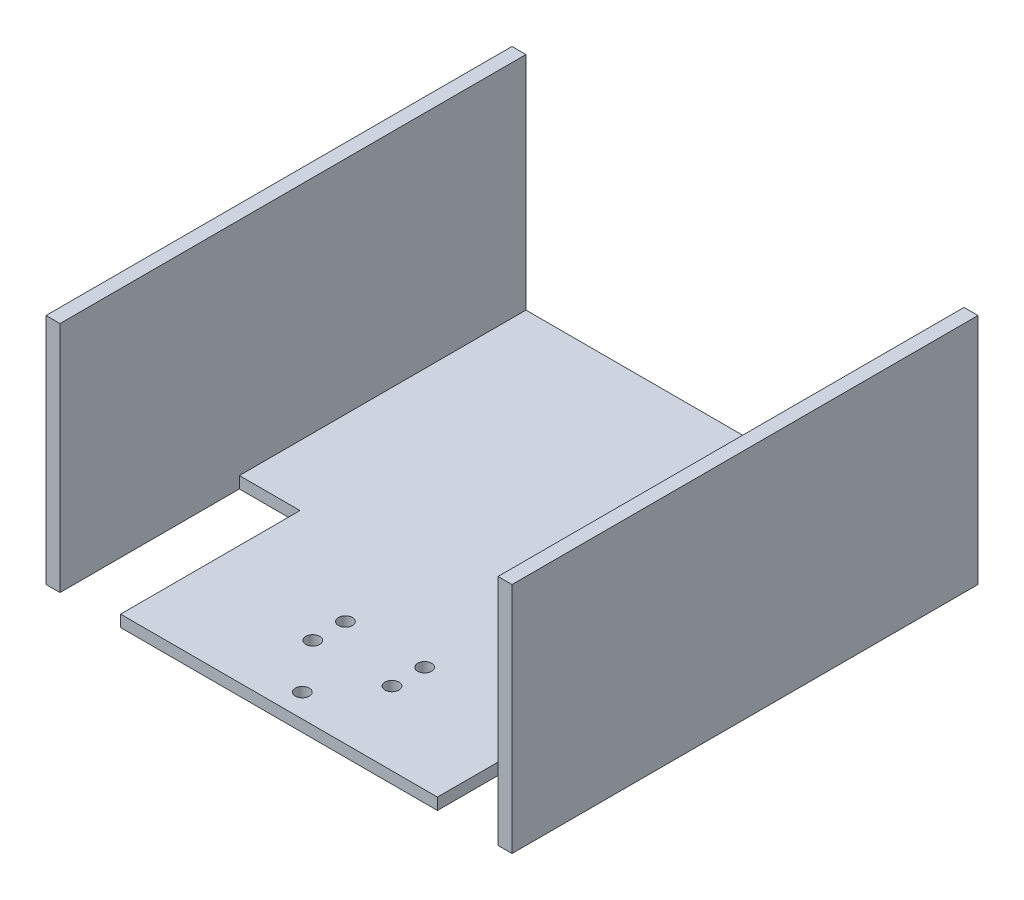
SolidWorks part; units mm, degrees
ref_plane "Alzado" through (0, 0, 0) normal (0, 0, 1) x (1, 0, 0)
ref_plane "Planta" through (0, 0, 0) normal (0, 1, 0) x (1, 0, 0)
ref_plane "Vista lateral" through (0, 0, 0) normal (1, 0, 0) x (0, 0, -1)
sketch "Croquis1" plane through (0, 0, 0) normal (0, 0, 1) x (1, 0, 0)
  line L0 (50, 0) -> (-50, 0)
  line L1 (-50, 0) -> (-50, 50)
  line L2 (-50, 50) -> (-47, 50)
  line L3 (-47, 50) -> (-47, 2.5)
  line L4 (-47, 2.5) -> (47, 2.5)
  line L5 (0, 2.5) -> (0, 0)
  line L6 (0, 0) -> (0, 13.9963) construction
  line L7 (47, 50) -> (47, 2.5)
  line L8 (50, 50) -> (47, 50)
  line L9 (50, 0) -> (50, 50)
  dimension "D1" = 50
  dimension "D2" = 50
  dimension "D3" = 3
  dimension "D4" = 2.5
extrude "Saliente-Extruir1" add sketch "Croquis1" against normal blind 100 contours L4 L7 L8 L9 L0 L1 L2 L3
sketch "Croquis2" plane through (0, 2.5, 0) normal (0, 1, 0) x (1, 0, 0)
  line L0 (0, 0) -> (0, 100) construction
  line L1 (-47, 0) -> (-34, 0)
  line L2 (-47, 0) -> (-47, 38.5)
  line L3 (-47, 38.5) -> (-34, 38.5)
  line L4 (-34, 0) -> (-34, 38.5)
  line L5 (-47, 100) -> (47, 100) construction
  line L6 (47, 38.5) -> (34, 38.5)
  line L7 (34, 0) -> (34, 38.5)
  line L8 (47, 0) -> (34, 0)
  line L9 (47, 0) -> (47, 38.5)
  dimension "D1" = 13
  dimension "D2" = 38.5
extrude "Cortar-Extruir2" cut sketch "Croquis2" against normal blind 10
ref_plane "Plano1" through (0, 2.5, 0) normal (0, 1, 0) x (1, 0, 0)
sketch "Croquis3" plane through (0, 2.5, 0) normal (0, 1, 0) x (1, 0, 0)
  line L0 (0, 0) -> (0, 100) construction
  line L1 (-47, 100) -> (47, 100) construction
  line L2 (-34, 0) -> (34, 0) construction
  circle A1 centre (0, 5) radius 1.5
  dimension "D1" = 3
  dimension "D2" = 5
extrude "Cortar-Extruir3" cut sketch "Croquis3" against normal blind 5
sketch "Croquis4" plane through (0, 2.5, 0) normal (0, 1, 0) x (1, 0, 0)
  line L0 (0, 0) -> (0, 100) construction
  line L1 (-47, 100) -> (47, 100) construction
  line L2 (0, 22.75) -> (-8.5, 22.75) construction
  line L3 (0, 15.75) -> (-8.5, 15.75) construction
  line L4 (-34, 19.25) -> (0, 19.25) construction
  line L6 (-34, 0) -> (-34, 38.5) construction
  circle A0 centre (-8.5, 22.75) radius 1.5
  circle A1 centre (-8.5, 15.75) radius 1.5
  circle A2 centre (8.5, 15.75) radius 1.5
  circle A3 centre (8.5, 22.75) radius 1.5
  dimension "D3" = 3
  dimension "D1" = 8.5
  dimension "D2" = 3.5
  dimension "D4" = 3.5
extrude "Cortar-Extruir4" cut sketch "Croquis4" against normal blind 10
